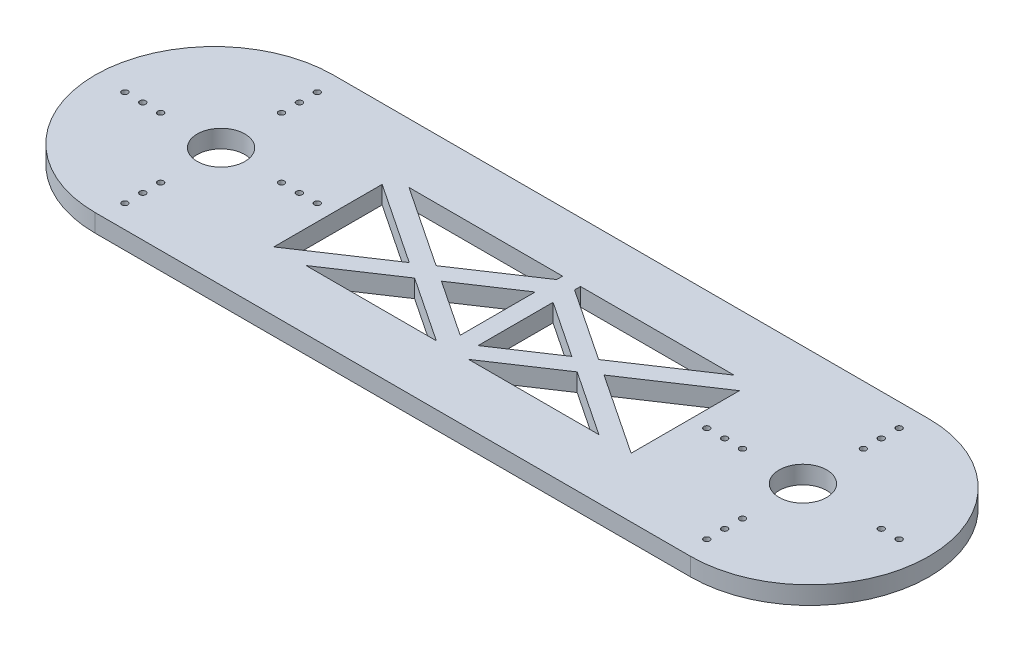
SolidWorks part; units mm, degrees
note: The reader was unsure of these and kept them because the rebuilt part matched: shared geometry of "Sketch1<3>".
ref_plane "Front Plane" through (0, 0, 0) normal (0, 0, 1) x (1, 0, 0)
ref_plane "Top Plane" through (0, 0, 0) normal (0, 1, 0) x (1, 0, 0)
ref_plane "Right Plane" through (0, 0, 0) normal (1, 0, 0) x (0, 0, -1)
sketch "Sketch1" plane through (0, 0, 0) normal (0, 1, 0) x (1, 0, 0)
  line L0 (-65, 0) -> (-62, 0)
  line L1 (-50, 20) -> (50, 20)
  line L2 (-50, 20) -> (-50, -20)
  line L3 (-50, -20) -> (50, -20)
  line L4 (50, 20) -> (50, -20)
  line L5 (-50, 20) -> (50, -20) construction
  line L6 (-50, -20) -> (50, 20) construction
  line L7 (-62, 0) -> (-59, 0)
  line L8 (-70, 0) -> (-65, 0)
  line L9 (-59, 0) -> (-48.85, 0)
  line L10 (-48.85, 10.15) -> (-48.85, 0)
  line L11 (-48.85, 13.15) -> (-48.85, 10.15)
  line L12 (-48.85, 16.15) -> (-48.85, 13.15)
  line L13 (-38.7, 0) -> (-48.85, 0)
  line L14 (-35.7, 0) -> (-38.7, 0)
  line L15 (-32.7, 0) -> (-35.7, 0)
  line L16 (-48.85, -10.15) -> (-48.85, 0)
  line L17 (-48.85, -13.15) -> (-48.85, -10.15)
  line L18 (-48.85, -16.15) -> (-48.85, -13.15)
  line L19 (0, 32.1937) -> (0, -35.5912)
  line L20 (48.85, -16.15) -> (48.85, -13.15)
  line L21 (70, 0) -> (65, 0)
  line L22 (65, 0) -> (62, 0)
  line L23 (62, 0) -> (59, 0)
  line L24 (48.85, -13.15) -> (48.85, -10.15)
  line L25 (48.85, -10.15) -> (48.85, 0)
  line L26 (48.85, 16.15) -> (48.85, 13.15)
  line L27 (48.85, 13.15) -> (48.85, 10.15)
  line L28 (48.85, 10.15) -> (48.85, 0)
  line L29 (59, 0) -> (48.85, 0)
  line L30 (32.7, 0) -> (35.7, 0)
  line L31 (35.7, 0) -> (38.7, 0)
  line L32 (38.7, 0) -> (48.85, 0)
  line L33 (0, 10) -> (-30, -10)
  line L34 (-30, 10) -> (30, 10)
  line L35 (-30, 10) -> (-30, -10)
  line L36 (-30, -10) -> (30, -10)
  line L37 (30, 10) -> (30, -10)
  line L38 (-30, 10) -> (30, -10) construction
  line L39 (-30, -10) -> (30, 10) construction
  line L40 (0, 10) -> (30, -10)
  line L41 (-1.5, 9) -> (-1.5, -10)
  line L42 (1.5, 9) -> (1.5, -10)
  line L43 (-24.5917, -10) -> (-1.5, 5.3944)
  line L44 (1.5, 5.3944) -> (24.5917, -10)
  line L45 (-30, 10) -> (-15, 0)
  line L46 (-30, 8.1972) -> (-16.3521, -0.9014)
  line L47 (-27.2958, 10) -> (-13.6479, 0.9014)
  line L48 (30, 8.1972) -> (16.3521, -0.9014)
  line L49 (27.2958, 10) -> (13.6479, 0.9014)
  line L50 (-1.5, 9) -> (-1.5, 10)
  line L51 (1.5, 9) -> (1.5, 10)
  line L52 (-13.6479, 0.9014) -> (-1.5, -7.1972)
  line L53 (-16.3521, -0.9014) -> (-2.7042, -10)
  line L54 (16.3521, -0.9014) -> (2.7042, -10)
  line L55 (13.6479, 0.9014) -> (1.5, -7.1972)
  arc A0 (-50, 20) -> (-50, -20) centre (-50, 0) ccw
  arc A1 (50, 20) -> (50, -20) centre (50, 0) cw
  circle A2 centre (-65, 0) radius 0.5
  circle A3 centre (-62, 0) radius 0.5
  circle A4 centre (-59, 0) radius 0.5
  circle A7 centre (-48.85, 10.15) radius 0.5
  circle A8 centre (-48.85, 13.15) radius 0.5
  circle A9 centre (-48.85, 16.15) radius 0.5
  circle A11 centre (-38.7, 0) radius 0.5
  circle A12 centre (-35.7, 0) radius 0.5
  circle A13 centre (-32.7, 0) radius 0.5
  circle A15 centre (-48.85, -10.15) radius 0.5
  circle A16 centre (-48.85, -13.15) radius 0.5
  circle A17 centre (-48.85, -16.15) radius 0.5
  circle A19 centre (-48.85, 0) radius 4
  circle A20 centre (48.85, -16.15) radius 0.5
  circle A21 centre (65, 0) radius 0.5
  circle A22 centre (62, 0) radius 0.5
  circle A23 centre (48.85, -13.15) radius 0.5
  circle A24 centre (48.85, -10.15) radius 0.5
  circle A25 centre (48.85, 16.15) radius 0.5
  circle A26 centre (48.85, 13.15) radius 0.5
  circle A27 centre (48.85, 10.15) radius 0.5
  circle A28 centre (32.7, 0) radius 0.5
  circle A29 centre (35.7, 0) radius 0.5
  circle A30 centre (38.7, 0) radius 0.5
  circle A31 centre (48.85, 0) radius 4
  point P0 (0, 0)
  point P45 (-48.85, 0)
  point P64 (0, 0)
  dimension "D6" = 1
  dimension "D8" = 60
  dimension "D9" = 8
  dimension "D1" = 100
  dimension "D2" = 40
  dimension "D3" = 3
  dimension "D4" = 10.15
  dimension "D5" = 5
  dimension "D7" = 4
  dimension "D10" = 20
  dimension "D11" = 3
  dimension "D12" = 3
  dimension "D13" = 3
  dimension "D14" = 1.5
  dimension "D15" = 1.5
extrude "Boss-Extrude1" add sketch "Sketch1" along normal blind 3
extrude "Boss-Extrude2" add sketch "Sketch1<3>" along normal blind 3 contours L33 L41 L36 L19 | L42 L40 L19 L36 | L40 L51 L34 | L50 L33 L34
sketch "Sketch1<3>" plane through (0, 0, 0) normal (0, 1, 0) x (1, 0, 0) same geometry as "Sketch1"
